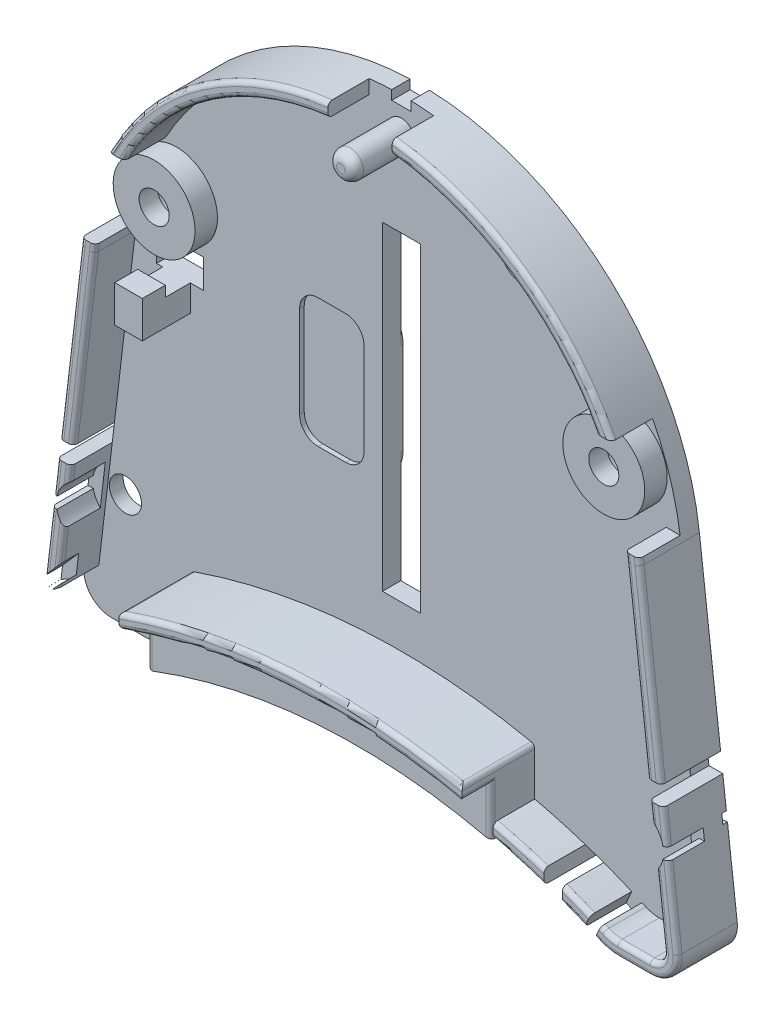
SolidWorks part; units mm, degrees
material "PW50:30:C1:0:1:2:Re:16:"
ref_plane "Plane1" through (0, 0, 0) normal (0, 0, 1) x (1, 0, 0)
ref_plane "Plane2" through (0, 0, 0) normal (0, 1, 0) x (1, 0, 0)
ref_plane "Plane3" through (0, 0, 0) normal (1, 0, 0) x (0, 0, -1)
sketch "Sketch1" plane through (0, 0, 0) normal (0, 0, 1) x (1, 0, 0)
  line L8 (31.5256, 3) -> (28.0259, 3)
  line L9 (-31.5256, 3) -> (-28.0259, 3)
  line L10 (34.5047, 6.3537) -> (30.3967, 40.9583)
  line L11 (-30.3967, 40.9583) -> (-34.5047, 6.3537)
  circle A4 centre (12.7584, 58.6048) radius 1.75
  circle A5 centre (-30, 15.3459) radius 1.75
  arc A12 (31.5256, 3) -> (34.5047, 6.3537) centre (31.5256, 6) ccw
  arc A13 (25.9509, 3.4509) -> (28.0259, 3) centre (28.0259, 8) ccw
  arc A14 (-34.5047, 6.3537) -> (-31.5256, 3) centre (-31.5256, 6) ccw
  arc A15 (-28.0259, 3) -> (-25.9509, 3.4509) centre (-28.0259, 8) ccw
  arc A16 (25.9509, 3.4509) -> (-25.9509, 3.4509) centre (0, -53.4421) ccw
  arc A17 (30.3967, 40.9583) -> (-30.3967, 40.9583) centre (0, 37.3499) ccw
  circle A18 centre (30, 15.3459) radius 1.75
  dimension "D2" = 3.5
  dimension "D3" = 3.5
  dimension "D4" = 3.5
extrude "Base-Extrude" add sketch "Sketch1" along normal blind 2
sketch "Sketch2" plane through (0, 0, 2) normal (0, 0, 1) x (1, 0, 0)
  line L4 (33.0151, 6.1768) -> (28.9072, 40.7815)
  line L5 (-28.9072, 40.7815) -> (-33.0151, 6.1768)
  line L6 (-31.5256, 4.5) -> (-28.0259, 4.5)
  line L7 (28.0259, 4.5) -> (31.5256, 4.5)
  line L8 (33.0151, 6.1768) -> (28.9072, 40.7815)
  line L9 (-28.9072, 40.7815) -> (-33.0151, 6.1768)
  line L10 (-31.5256, 4.5) -> (-28.0259, 4.5)
  line L11 (28.0259, 4.5) -> (31.5256, 4.5)
  line L12 (34.5047, 6.3537) -> (30.3967, 40.9583)
  line L13 (-30.3967, 40.9583) -> (-34.5047, 6.3537)
  line L14 (-31.5256, 3) -> (-28.0259, 3)
  line L15 (28.0259, 3) -> (31.5256, 3)
  line L16 (34.5047, 6.3537) -> (30.3967, 40.9583)
  line L17 (-30.3967, 40.9583) -> (-34.5047, 6.3537)
  line L18 (-31.5256, 3) -> (-28.0259, 3)
  line L19 (28.0259, 3) -> (31.5256, 3)
  arc A7 (31.5256, 4.5) -> (33.0151, 6.1768) centre (31.5256, 6) ccw
  arc A8 (28.9072, 40.7815) -> (-28.9072, 40.7815) centre (0, 37.3499) ccw
  arc A9 (-33.0151, 6.1768) -> (-31.5256, 4.5) centre (-31.5256, 6) ccw
  arc A10 (-28.0259, 4.5) -> (-26.5734, 4.8156) centre (-28.0259, 8) ccw
  arc A11 (26.5734, 4.8156) -> (-26.5734, 4.8156) centre (0, -53.4421) ccw
  arc A12 (26.5734, 4.8156) -> (28.0259, 4.5) centre (28.0259, 8) ccw
  arc A13 (31.5256, 4.5) -> (33.0151, 6.1768) centre (31.5256, 6) ccw
  arc A14 (28.9072, 40.7815) -> (-28.9072, 40.7815) centre (0, 37.3499) ccw
  arc A15 (-33.0151, 6.1768) -> (-31.5256, 4.5) centre (-31.5256, 6) ccw
  arc A16 (-28.0259, 4.5) -> (-26.5734, 4.8156) centre (-28.0259, 8) ccw
  arc A17 (26.5734, 4.8156) -> (-26.5734, 4.8156) centre (0, -53.4421) ccw
  arc A18 (26.5734, 4.8156) -> (28.0259, 4.5) centre (28.0259, 8) ccw
  arc A19 (31.5256, 3) -> (34.5047, 6.3537) centre (31.5256, 6) ccw
  arc A20 (30.3967, 40.9583) -> (-30.3967, 40.9583) centre (0, 37.3499) ccw
  arc A21 (-34.5047, 6.3537) -> (-31.5256, 3) centre (-31.5256, 6) ccw
  arc A22 (-28.0259, 3) -> (-25.9509, 3.4509) centre (-28.0259, 8) ccw
  arc A23 (25.9509, 3.4509) -> (-25.9509, 3.4509) centre (0, -53.4421) ccw
  arc A24 (25.9509, 3.4509) -> (28.0259, 3) centre (28.0259, 8) ccw
  arc A25 (31.5256, 3) -> (34.5047, 6.3537) centre (31.5256, 6) ccw
  arc A26 (30.3967, 40.9583) -> (-30.3967, 40.9583) centre (0, 37.3499) ccw
  arc A27 (-34.5047, 6.3537) -> (-31.5256, 3) centre (-31.5256, 6) ccw
  arc A28 (-28.0259, 3) -> (-25.9509, 3.4509) centre (-28.0259, 8) ccw
  arc A29 (25.9509, 3.4509) -> (-25.9509, 3.4509) centre (0, -53.4421) ccw
  arc A30 (25.9509, 3.4509) -> (28.0259, 3) centre (28.0259, 8) ccw
  dimension "D1" = 1.5
  dimension "D2" = 0
extrude "Boss-Extrude1" add sketch "Sketch2" along normal blind 4.5
fillet "Fillet3" radius 0.5 20 edges at (33.7685, 4.0076, 6.5) (32.4507, 23.656, 6.5) (0, 67.96, 6.5) (-32.4507, 23.656, 6.5) (-33.7685, 4.0076, 6.5) (-29.7758, 3, 6.5) (-26.9642, 3.114, 6.5) (26.9642, 3.114, 6.5) (29.7758, 3, 6.5) (0, 10.59, 6.5) (0, 9.09, 6.5) (32.647, 5.0038, 6.5) (30.9612, 23.4792, 6.5) (0, 66.46, 6.5) (-30.9612, 23.4792, 6.5) (-32.647, 5.0038, 6.5) (-29.7758, 4.5, 6.5) (-27.2827, 4.5798, 6.5) (27.2827, 4.5798, 6.5) (29.7758, 4.5, 6.5)
extrude "Cut-Extrude3" cut sketch "Sketch4" against normal up to surface (4.5 mm away)
sketch "Sketch4" plane through (0, 0, 2) normal (0, 0, 1) x (1, 0, 0)
  line L0 (0, 0) -> (0, 77.2938) construction
  line L1 (-3.5, 67.7592) -> (-3.5, 66.2488)
  line L2 (3.5, 67.7592) -> (3.5, 66.2488)
  arc A0 (28.9072, 40.7815) -> (-28.9072, 40.7815) centre (0, 37.3499) ccw construction
  arc A1 (-30.3967, 40.9583) -> (30.3967, 40.9583) centre (0, 37.3499) ccw construction
  arc A2 (3.5, 66.2488) -> (-3.5, 66.2488) centre (0, 37.3499) ccw
  arc A4 (3.5, 67.7592) -> (-3.5, 67.7592) centre (0, 37.3499) ccw
  dimension "D1" = 7
sketch "Sketch3" plane through (0, 0, 2) normal (0, 0, 1) x (1, 0, 0)
  line L0 (0, 0) -> (0, 74.8209) construction
  line L1 (-2.06, 54.96) -> (2.06, 54.96)
  line L2 (2.06, 54.96) -> (2.06, 20.21)
  line L3 (2.06, 20.21) -> (-2.06, 20.21)
  line L4 (-2.06, 54.96) -> (-2.06, 20.21)
  arc A0 (25.9509, 3.4509) -> (-25.9509, 3.4509) centre (0, -53.4421) ccw construction
  point P8 (0, 20.21)
  point P9 (0, 54.96)
  dimension "D1" = 34.75
  dimension "D2" = 4.12
  dimension "D3" = 11.12
extrude "Cut-Extrude1" cut sketch "Sketch3" against normal through all
sketch "Sketch5" plane through (0, 0, 2) normal (0, 0, 1) x (1, 0, 0)
  line L0 (0, 0) -> (0, 78.193) construction
  circle A0 centre (0, 64.32) radius 1.46
  arc A1 (3.5, 67.7592) -> (-3.5, 67.7592) centre (0, 37.3499) ccw construction
  dimension "D1" = 2.92
  dimension "D2" = 5.1
extrude "Boss-Extrude2" add sketch "Sketch5" along normal blind 6.58
fillet "Fillet1" radius 1 1 edges at (1.46, 64.32, 8.58)
sketch "Sketch7"
  line L0 (-2, 66.2488) -> (-2, 40.7815) construction
  line L1 (-2, 51.1716) -> (-2, 41.6526)
  line L2 (-6.5, 51.1716) -> (-2, 51.1716)
  line L3 (-6.5, 41.6526) -> (-2, 41.6526)
  line L4 (-6.5, 67.2559) -> (-6.5, 40.8994) construction
  line L5 (-6.5, 51.1716) -> (-6.5, 41.6526)
extrude "Boss-Extrude4" add sketch "Sketch6" against normal offset from surface (4.44 mm away) 2.44
sketch "Sketch6" plane through (0, 0, 0) normal (0, 0, -1) x (-1, 0, 0)
  line L0 (0, 0) -> (0, 77.0388) construction
  line L1 (-2.06, 20.21) -> (2.06, 20.21) construction
  circle A0 centre (-24.4419, 46.39) radius 4.45
  circle A1 centre (24.4419, 46.39) radius 4.45
  arc A3 (30.3967, 40.9583) -> (-30.3967, 40.9583) centre (0, 37.3499) ccw construction
  dimension "D1" = 8.9
  dimension "D2" = 0.1
  dimension "D3" = 26.18
extrude "Cut-Extrude4" cut sketch "Sketch7" against normal through all and the other way through all
sketch "Sketch8" plane through (0, 0, 0) normal (1, 0, 0) x (0, 0, -1)
  line L0 (-6.5, 19.5424) -> (-2, 19.5424)
  line L1 (-6.5, 21.5424) -> (-2, 21.5424)
  line L2 (-2, 6.1768) -> (-2, 40.7815) construction
  line L3 (-2, 19.5424) -> (-2, 21.5424)
  line L4 (-6.5, 6.2947) -> (-6.5, 40.8994) construction
  line L5 (-6.5, 19.5424) -> (-6.5, 21.5424)
  dimension "D1" = 2
extrude "Cut-Extrude5" cut sketch "Sketch8" against normal through all and the other way through all
sketch "Sketch9" plane through (0, 0, 0) normal (0, 0, -1) x (-1, 0, 0)
  line L0 (0, 0) -> (0, 73.4075) construction
  circle A0 centre (24.4419, 46.39) radius 2.95
  circle A1 centre (-24.4419, 46.39) radius 2.95
  dimension "D1" = 5.9
extrude "Cut-Extrude6" cut sketch "Sketch9" against normal blind 2.44
sketch "Sketch10" plane through (0, 0, 0) normal (0, 0, -1) x (-1, 0, 0)
  line L0 (0, 0) -> (0, 75.2232) construction
  circle A0 centre (24.4419, 46.39) radius 1.635
  circle A1 centre (-24.4419, 46.39) radius 1.635
  dimension "D1" = 3.27
extrude "Cut-Extrude7" cut sketch "Sketch10" against normal through all
sketch "Sketch11" plane through (0, 0, 2) normal (0, 0, 1) x (1, 0, 0)
  line L0 (0, 0) -> (0, 73.4075) construction
  line L1 (-32.939, 19.5424) -> (-32.7016, 21.5424) construction
  line L2 (-32.939, 19.5424) -> (-32.7016, 21.5424)
  line L3 (-31.4285, 19.5424) -> (-31.932, 19.5424) construction
  line L4 (-32.4355, 19.5424) -> (-31.932, 19.5424) construction
  line L5 (-32.4355, 19.5424) -> (-32.939, 19.5424) construction
  line L6 (-31.6946, 21.5424) -> (-31.1911, 21.5424) construction
  line L7 (-32.1981, 21.5424) -> (-31.6946, 21.5424) construction
  line L8 (-32.7016, 21.5424) -> (-32.1981, 21.5424) construction
  line L9 (-31.4285, 19.5424) -> (-31.932, 19.5424)
  line L10 (-32.4355, 19.5424) -> (-31.932, 19.5424)
  line L11 (-32.4355, 19.5424) -> (-32.939, 19.5424)
  line L12 (-31.6946, 21.5424) -> (-31.1911, 21.5424)
  line L13 (-32.1981, 21.5424) -> (-31.6946, 21.5424)
  line L14 (-32.7016, 21.5424) -> (-32.1981, 21.5424)
  line L15 (-31.1911, 21.5424) -> (-31.4285, 19.5424)
  line L16 (31.1911, 21.5424) -> (31.4285, 19.5424)
  line L17 (32.7016, 21.5424) -> (32.939, 19.5424) construction
  line L18 (32.939, 19.5424) -> (32.4355, 19.5424) construction
  line L19 (31.932, 19.5424) -> (32.4355, 19.5424) construction
  line L20 (31.932, 19.5424) -> (31.4285, 19.5424) construction
  line L21 (32.1981, 21.5424) -> (32.7016, 21.5424) construction
  line L22 (31.6946, 21.5424) -> (32.1981, 21.5424) construction
  line L23 (31.1911, 21.5424) -> (31.6946, 21.5424) construction
  line L24 (32.7016, 21.5424) -> (32.939, 19.5424)
  line L25 (32.939, 19.5424) -> (32.4355, 19.5424)
  line L26 (31.932, 19.5424) -> (32.4355, 19.5424)
  line L27 (31.932, 19.5424) -> (31.4285, 19.5424)
  line L28 (32.1981, 21.5424) -> (32.7016, 21.5424)
  line L29 (31.6946, 21.5424) -> (32.1981, 21.5424)
  line L30 (31.1911, 21.5424) -> (31.6946, 21.5424)
extrude "Cut-Extrude8" cut sketch "Sketch11" against normal through all
sketch "Sketch12" plane through (0, 0, 2) normal (0, 0, 1) x (1, 0, 0)
  line L0 (0, 0) -> (0, 81.4772) construction
  line L1 (-1.05, 66.9333) -> (1.05, 66.9333)
  line L2 (-1.05, 67.942) -> (-1.05, 66.9333)
  line L3 (1.05, 67.942) -> (1.05, 66.9333)
  line L4 (-0.6081, 66.9333) -> (0.8919, 66.9333) construction
  arc A2 (3.5, 67.7592) -> (-3.5, 67.7592) centre (0, 37.3499) ccw construction
  arc A3 (1.05, 67.942) -> (-1.05, 67.942) centre (0, 37.3499) ccw
  dimension "D1" = 2.1
extrude "Cut-Extrude9" cut sketch "Sketch12" against normal through all
sketch "Sketch13" plane through (0, 0, 0) normal (0, 0, -1) x (-1, 0, 0)
  line L0 (21.4919, 41.94) -> (26.6119, 41.94)
  line L1 (21.4919, 41.94) -> (21.4919, 38.8)
  line L2 (26.6119, 38.8) -> (21.4919, 38.8)
  line L3 (26.6119, 38.8) -> (26.6119, 41.94)
  circle A0 centre (24.4419, 46.39) radius 4.45 construction
  circle A2 centre (24.4419, 46.39) radius 2.95 construction
  dimension "D1" = 5.12
  dimension "D2" = 3.14
extrude "Cut-Extrude10" cut sketch "Sketch13" against normal through all
sketch "Sketch14" plane through (0, 0, 2) normal (0, 0, 1) x (1, 0, 0)
  line L0 (-25.9419, 39.94) -> (-22.9419, 39.94)
  line L1 (-25.9419, 39.94) -> (-25.9419, 35.94)
  line L2 (-22.9419, 35.94) -> (-25.9419, 35.94)
  line L3 (-22.9419, 35.94) -> (-22.9419, 39.94)
  line L6 (-24.4419, 46.39) -> (-24.4419, 39.94) construction
  line L7 (-24.4419, 41.94) -> (-21.4919, 41.94) construction
  dimension "D1" = 4
  dimension "D2" = 3
  dimension "D3" = 2
extrude "Boss-Extrude5" add sketch "Sketch14" along normal blind 5.22
sketch "Sketch15" plane through (0, 0, 0) normal (0, 0, -1) x (-1, 0, 0)
  line L0 (21.4919, 41.94) -> (26.6119, 41.94) construction
  line L1 (26.6119, 38.8) -> (26.6119, 41.94) construction
  line L2 (26.6119, 38.8) -> (21.4919, 38.8) construction
  line L3 (21.4919, 41.94) -> (21.4919, 38.8) construction
  line L4 (21.4919, 41.94) -> (26.6119, 41.94)
  line L5 (26.6119, 38.8) -> (26.6119, 41.94)
  line L6 (26.6119, 38.8) -> (21.4919, 38.8)
  line L7 (21.4919, 41.94) -> (21.4919, 38.8)
extrude "Cut-Extrude11" cut sketch "Sketch15" against normal offset from surface (4.72 mm away) 2.5 up to face at (-24.4419, 37.94, 7.22)
sketch "Sketch16" plane through (0, 0, 2) normal (0, 0, 1) x (1, 0, 0)
  line L0 (19.9919, 5.8081) -> (19.9919, 7.3891)
  line L1 (21.9919, 6.695) -> (21.9919, 5.0952)
  circle A1 centre (24.4419, 46.39) radius 4.45 construction
  arc A2 (26.5734, 4.8156) -> (-26.5734, 4.8156) centre (0, -53.4421) ccw construction
  arc A3 (21.9919, 6.695) -> (19.9919, 7.3891) centre (0, -53.4421) ccw
  arc A4 (25.9509, 3.4509) -> (-25.9509, 3.4509) centre (0, -53.4421) ccw construction
  arc A5 (21.9919, 5.0952) -> (19.9919, 5.8081) centre (0, -53.4421) ccw
  dimension "D1" = 2
extrude "Cut-Extrude12" cut sketch "Sketch16" against normal through all and the other way through all
sketch "Sketch17" plane through (0, 0, 0) normal (0, 0, -1) x (-1, 0, 0)
  circle A4 centre (30, 15.3459) radius 2.75
  circle A5 centre (30, 15.3459) radius 2.75
  circle A6 centre (-30, 15.3459) radius 2.75
  circle A7 centre (-30, 15.3459) radius 2.75
  circle A8 centre (-12.7584, 58.6048) radius 2.75
  circle A9 centre (-12.7584, 58.6048) radius 2.75
  dimension "D1" = 1
  dimension "D2" = 1
  dimension "D3" = 1
extrude "Cut-Extrude13" cut sketch "Sketch17" against normal blind 0.5
sketch "Sketch18" plane through (0, 0, 0) normal (0, 0, -1) x (-1, 0, 0)
  line L0 (2.06, 46.3499) -> (13.06, 46.3499)
  line L1 (2.06, 46.3499) -> (2.06, 28.3499)
  line L2 (13.06, 28.3499) -> (2.06, 28.3499)
  line L3 (13.06, 28.3499) -> (13.06, 46.3499)
  line L4 (2.06, 54.96) -> (2.06, 20.21) construction
  line L5 (-14.0172, 37.3499) -> (2.06, 37.3499) construction
  dimension "D1" = 11
  dimension "D2" = 18
extrude "Boss-Extrude6" add sketch "Sketch18" along normal blind 0.24
fillet "Fillet4" radius 4 4 edges at (-2.06, 46.3499, -0.12) (-2.06, 28.3499, -0.12) (-13.06, 28.3499, -0.12) (-13.06, 46.3499, -0.12)
sketch "Sketch19" plane through (0, 0, 2) normal (0, 0, 1) x (1, 0, 0)
  line L0 (14.4919, 14.0517) -> (14.4919, 7.3876)
  line L1 (-22.8069, 11.7137) -> (-22.8069, 4.7825)
  arc A0 (19.9919, 5.8081) -> (-25.9509, 3.4509) centre (0, -53.4421) ccw construction
  arc A1 (22.07, 11.967) -> (-28.6484, 9.3647) centre (0, -53.4421) ccw
  arc A2 (14.4919, 14.0517) -> (-22.8069, 11.7137) centre (0, -53.4421) ccw
  arc A3 (14.4919, 7.3876) -> (-22.8069, 4.7825) centre (0, -53.4421) ccw
  circle A4 centre (-24.4419, 46.39) radius 1.635 construction
  dimension "D2" = 7.5
  dimension "D1" = 6.5
extrude "Boss-Extrude7" add sketch "Sketch19" along normal blind 4.8
sketch "Sketch20" plane through (0, 0, 6.8) normal (0, 0, 1) x (1, 0, 0)
  line L0 (-22.8069, 11.7137) -> (-22.8069, 4.7825) construction
  line L1 (-22.8069, 11.7137) -> (-22.8069, 10.1223)
  line L3 (14.4919, 14.0517) -> (14.4919, 7.3876) construction
  line L4 (14.4919, 14.0517) -> (14.4919, 12.5167)
  arc A0 (14.4919, 14.0517) -> (-22.8069, 11.7137) centre (0, -53.4421) ccw construction
  arc A1 (14.177, 12.5851) -> (-22.3113, 10.2979) centre (0, -53.4421) ccw
  arc A2 (14.4919, 12.5167) -> (-22.8069, 10.1223) centre (0, -53.4421) ccw
  arc A3 (14.4919, 14.0517) -> (-22.8069, 11.7137) centre (0, -53.4421) ccw
  dimension "D1" = 1.5
extrude "Boss-Extrude8" add sketch "Sketch20" along normal blind 3.1
sketch "Sketch21" plane through (0, 0, 0) normal (0, 0, -1) x (-1, 0, 0)
  line L1 (-12.4919, 14.0517) -> (-12.4919, 8.9285)
  line L2 (-12.4919, 12.4157) -> (-12.4919, 9.8694)
  line L3 (20.8069, 11.7137) -> (20.8069, 6.3906)
  line L4 (20.8069, 10.279) -> (20.8069, 7.6436)
  arc A1 (26.7809, 5.2705) -> (-20.6313, 7.7031) centre (0, -53.4421) ccw
  arc A2 (20.8069, 7.6436) -> (-12.4919, 9.8694) centre (0, -53.4421) ccw
  arc A3 (22.1461, 9.826) -> (-14.072, 12.0963) centre (0, -53.4421) ccw
  arc A4 (20.8069, 10.279) -> (-12.4919, 12.4157) centre (0, -53.4421) ccw
  dimension "D1" = 2
  dimension "D2" = 2
  dimension "D3" = 2
  dimension "D4" = 2
extrude "Cut-Extrude14" cut sketch "Sketch21" against normal offset from surface (4.8 mm away) 2
fillet "Fillet9" radius 0.5 8 edges at (-22.8069, 11.7137, 5.95) (14.4919, 14.0517, 5.95) (-4.3265, 13.9513, 9.9) (-22.8069, 10.1223, 8.35) (14.4919, 12.5167, 8.35) (-4.3187, 15.4548, 9.9) (-4.3039, 10.9463, 0) (-4.2926, 13.4524, 0)
sketch "Sketch22" plane through (0, 0, 2) normal (0, 0, 1) x (1, 0, 0)
  line L0 (-34.5047, 6.3537) -> (-32.939, 19.5424) construction
  line L1 (-34.5047, 6.3537) -> (-32.939, 19.5424) construction
  line L2 (-22.8069, 10.829) -> (-22.8069, 4.7825) construction
  line L3 (-22.8069, 11.7137) -> (-22.8069, 4.7825)
  line L4 (-28.0259, 3) -> (-31.5256, 3) construction
  line L5 (-28.0259, 3) -> (-31.5256, 3)
  arc A1 (-28.0259, 3) -> (-25.9509, 3.4509) centre (-28.0259, 8) ccw construction
  arc A2 (-22.8069, 11.7137) -> (-34.5054, 6.3476) centre (0, -53.4421) ccw
  arc A4 (-22.8069, 4.7825) -> (-25.9509, 3.4509) centre (0, -53.4421) ccw construction
  arc A5 (-34.5047, 6.3537) -> (-31.5256, 3) centre (-31.5256, 6) ccw construction
  arc A6 (-22.8069, 4.7825) -> (-25.9509, 3.4509) centre (0, -53.4421) ccw
  arc A7 (-34.5054, 6.3476) -> (-31.5256, 3) centre (-31.5256, 6) ccw
  arc A8 (-28.0259, 3) -> (-25.9509, 3.4509) centre (-28.0259, 8) ccw
extrude "Cut-Extrude15" cut sketch "Sketch22" along normal through all
fillet "Fillet10" radius 0.5 5 edges at (14.4919, 8.1583, 6.5) (14.4919, 8.7686, 6.3626) (-22.8069, 4.7825, 4.4) (-22.8069, 7.8057, 6.8) (14.4919, 10.2616, 6.8)
sketch "Sketch23" plane through (0, 0, 2) normal (0, 0, 1) x (1, 0, 0)
  line L5 (-4.06, 54.96) -> (-4.06, 20.21)
  line L6 (-4.06, 42.3499) -> (-4.06, 32.3499)
  line L9 (-9.06, 30.3499) -> (-6.06, 30.3499)
  line L10 (-11.06, 32.3499) -> (-11.06, 42.3499)
  line L11 (-6.06, 44.3499) -> (-9.06, 44.3499)
  line L12 (-9.06, 30.3499) -> (-6.06, 30.3499)
  line L13 (-11.06, 32.3499) -> (-11.06, 42.3499)
  line L14 (-6.06, 44.3499) -> (-9.06, 44.3499)
  arc A6 (-11.06, 32.3499) -> (-9.06, 30.3499) centre (-9.06, 32.3499) ccw
  arc A7 (-9.06, 44.3499) -> (-11.06, 42.3499) centre (-9.06, 42.3499) ccw
  arc A8 (-11.06, 32.3499) -> (-9.06, 30.3499) centre (-9.06, 32.3499) ccw
  arc A9 (-9.06, 44.3499) -> (-11.06, 42.3499) centre (-9.06, 42.3499) ccw
  arc A11 (-6.06, 30.3499) -> (-4.06, 32.3499) centre (-6.06, 32.3499) ccw
  arc A12 (-6.06, 30.3499) -> (-4.06, 32.3499) centre (-6.06, 32.3499) ccw
  arc A13 (-4.06, 42.3499) -> (-6.06, 44.3499) centre (-6.06, 42.3499) ccw
  arc A14 (-4.06, 42.3499) -> (-6.06, 44.3499) centre (-6.06, 42.3499) ccw
  dimension "D1" = 2
  dimension "D2" = 2
  dimension "D3" = 2
  dimension "D4" = 2
extrude "Cut-Extrude16" cut sketch "Sketch23" against normal blind 0.5
sketch "Sketch26" plane through (0, 0, 2) normal (0, 0, 1) x (1, 0, 0)
  line L0 (25.5557, 3.6295) -> (29.3849, 12.4096) construction
  line L1 (25.5557, 3.6295) -> (26.1554, 5.0045)
  line L2 (24.4374, 4.1172) -> (28.2666, 12.8973) construction
  line L3 (24.4374, 4.1172) -> (25.0371, 5.4922)
  arc A0 (26.5734, 4.8156) -> (21.9919, 6.695) centre (0, -53.4421) ccw construction
  arc A1 (26.1554, 5.0045) -> (25.0371, 5.4922) centre (0, -53.4421) ccw
  arc A2 (25.9509, 3.4509) -> (21.9919, 5.0952) centre (0, -53.4421) ccw construction
  arc A3 (25.5557, 3.6295) -> (24.4374, 4.1172) centre (0, -53.4421) ccw
extrude "Cut-Extrude22" cut sketch "Sketch26" along normal blind 4.53
sketch "Sketch28" plane through (0, 0, 4.5) normal (0, 0, -1) x (-1, 0, 0)
  line L0 (35.1018, 6.8709) -> (34.1797, 6.0721) construction
  line L1 (28.2693, 12.8954) -> (34.1797, 6.0721) construction
  line L2 (30.3424, 12.3655) -> (35.1018, 6.8709) construction
  line L3 (35.1018, 6.8709) -> (34.1797, 6.0721)
  line L4 (32.8446, 7.6135) -> (34.1797, 6.0721)
  line L5 (32.5883, 9.7727) -> (35.1018, 6.8709)
  line L6 (31.4285, 19.5424) -> (32.8874, 7.2526) construction
  line L7 (32.5883, 9.7727) -> (32.8446, 7.6135)
extrude "Cut-Extrude24" cut sketch "Sketch28" against normal up to surface (4.7 mm away)
sketch "Sketch29" plane through (0, 0, 2.56) normal (0, 0, -1) x (-1, 0, 0)
  line L0 (-32.9373, 15.9559) -> (-33.3648, 15.9559) construction
  line L1 (-32.9373, 14.7359) -> (-33.5096, 14.7359) construction
  line L2 (-32.9373, 15.9559) -> (-33.3648, 15.9559)
  line L3 (-32.9373, 14.7359) -> (-33.5096, 14.7359)
  line L4 (-33.3648, 15.9559) -> (-33.5096, 14.7359)
  circle A0 centre (-30, 15.3459) radius 3 construction
  arc A1 (-32.9373, 14.7359) -> (-32.9373, 15.9559) centre (-30, 15.3459) ccw
extrude "Cut-Extrude25" cut sketch "Sketch29" against normal up to surface (21.34 mm away)
sketch "Sketch30" plane through (0, 0, 2.56) normal (0, 0, -1) x (-1, 0, 0)
  line L0 (32.9373, 15.9559) -> (33.3648, 15.9559) construction
  line L1 (32.9373, 14.7359) -> (33.5096, 14.7359) construction
  line L2 (32.9373, 15.9559) -> (33.3648, 15.9559)
  line L3 (32.9373, 14.7359) -> (33.5096, 14.7359)
  line L4 (33.3648, 15.9559) -> (33.5096, 14.7359)
  arc A0 (30.3424, 12.3655) -> (27.0989, 16.1099) centre (30, 15.3459) ccw construction
  arc A1 (27.0989, 16.1099) -> (32.9373, 14.7359) centre (30, 15.3459) ccw
  arc A2 (32.9373, 15.9559) -> (27.0989, 16.1099) centre (30, 15.3459) ccw
extrude "Cut-Extrude26" cut sketch "Sketch30" against normal up to surface (18.34 mm away)
sketch "Sketch31" plane through (0, 0, 0) normal (0, 0, -1) x (-1, 0, 0)
  line L0 (-32.2068, 15.1043) -> (-32.9964, 15.198) construction
  line L1 (-32.0889, 16.0973) -> (-32.8785, 16.1911) construction
  line L2 (-34.8205, 12.176) -> (-32.9219, 28.1693) construction
  line L3 (-34.3235, 16.3626) -> (-32.8785, 16.1911) construction
  line L4 (-34.4414, 15.3696) -> (-32.9964, 15.198) construction
  line L5 (-32.7443, 15.1681) -> (-32.9964, 15.198)
  line L6 (-32.6264, 16.1611) -> (-32.8785, 16.1911)
  line L7 (-34.4414, 15.3696) -> (-34.3235, 16.3626)
  line L8 (-34.3235, 16.3626) -> (-32.8785, 16.1911)
  line L9 (-34.4414, 15.3696) -> (-32.9964, 15.198)
  line L10 (32.9219, 28.1693) -> (34.8205, 12.176) construction
  line L11 (34.4414, 15.3696) -> (32.9964, 15.198) construction
  line L12 (32.2068, 15.1043) -> (32.9964, 15.198) construction
  line L13 (32.0889, 16.0973) -> (32.8785, 16.1911) construction
  line L14 (34.3235, 16.3626) -> (32.8785, 16.1911) construction
  line L15 (34.3235, 16.3626) -> (34.4414, 15.3696)
  line L16 (34.4414, 15.3696) -> (32.9964, 15.198)
  line L17 (32.7443, 15.1681) -> (32.9964, 15.198)
  line L18 (32.6264, 16.1611) -> (32.8785, 16.1911)
  line L19 (34.3235, 16.3626) -> (32.8785, 16.1911)
  circle A0 centre (30, 15.3459) radius 2.75 construction
  circle A1 centre (-30, 15.3459) radius 2.75 construction
  arc A2 (32.6264, 16.1611) -> (32.7443, 15.1681) centre (30, 15.3459) ccw
  arc A3 (-32.7443, 15.1681) -> (-32.6264, 16.1611) centre (-30, 15.3459) ccw
extrude "Cut-Extrude27" cut sketch "Sketch31" against normal up to surface (0.5 mm away) up to face at (28.25, 15.3459, 0.5)
